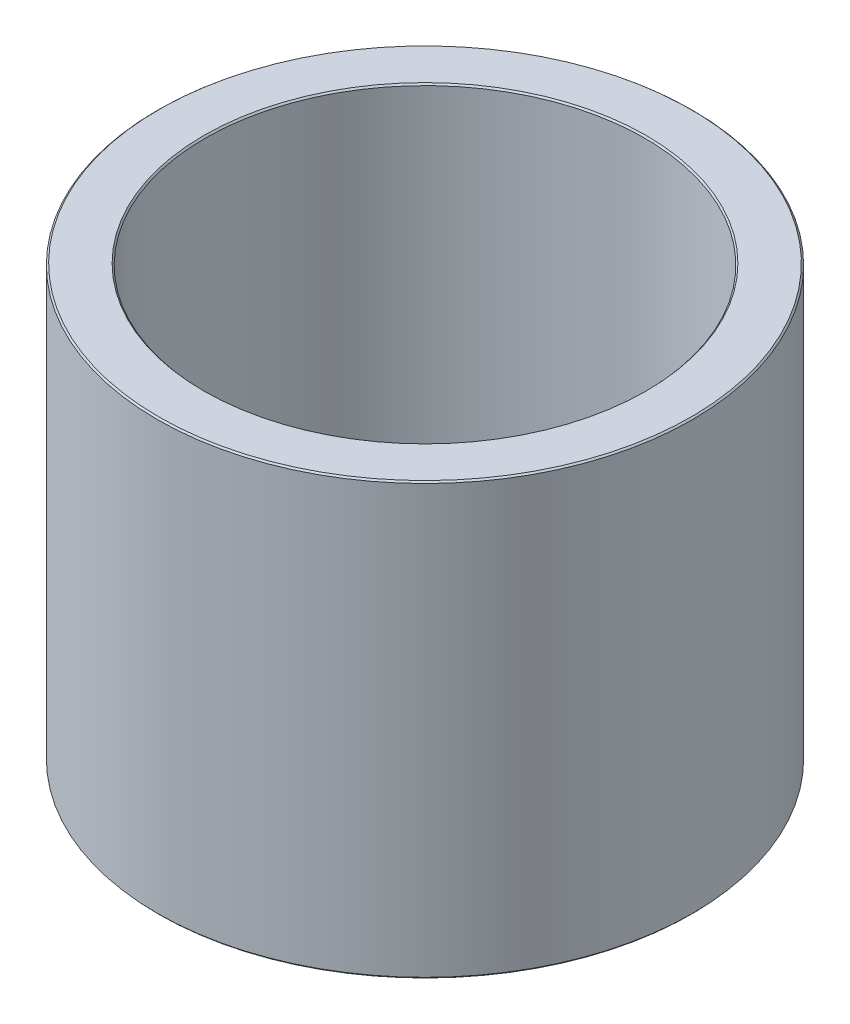
SolidWorks part; units mm, degrees
ref_plane "Front Plane" through (0, 0, 0) normal (0, 0, 1) x (1, 0, 0)
ref_plane "Top Plane" through (0, 0, 0) normal (0, 1, 0) x (1, 0, 0)
ref_plane "Right Plane" through (0, 0, 0) normal (1, 0, 0) x (0, 0, -1)
sketch "Sketch1" plane through (0, 0, 0) normal (0, 1, 0) x (1, 0, 0)
  circle A0 centre (0, 0) radius 47.5
  dimension "SLEEVE_OD" = 95
extrude "Boss-Extrude1" add sketch "Sketch1" along normal blind 76.407
sketch "Sketch2" plane through (0, 0, 0) normal (0, 1, 0) x (1, 0, 0)
  circle A0 centre (0, 0) radius 38.9967
  dimension "BORE_D" = 77.9934
extrude "Cut-Extrude1" cut sketch "Sketch2" along normal through all
chamfer "Chamfer1" distance 0.2558 angle 47.665 4 edges at (0, 76.407, 38.9967) (0, 0, 38.9967) (0, 0, 47.5) (0, 76.407, 47.5) first distance on face at (0, 76.407, 38.9967) first distance on face at (0, 0, 38.9967) first distance on face at (0, 76.407, 47.5)
